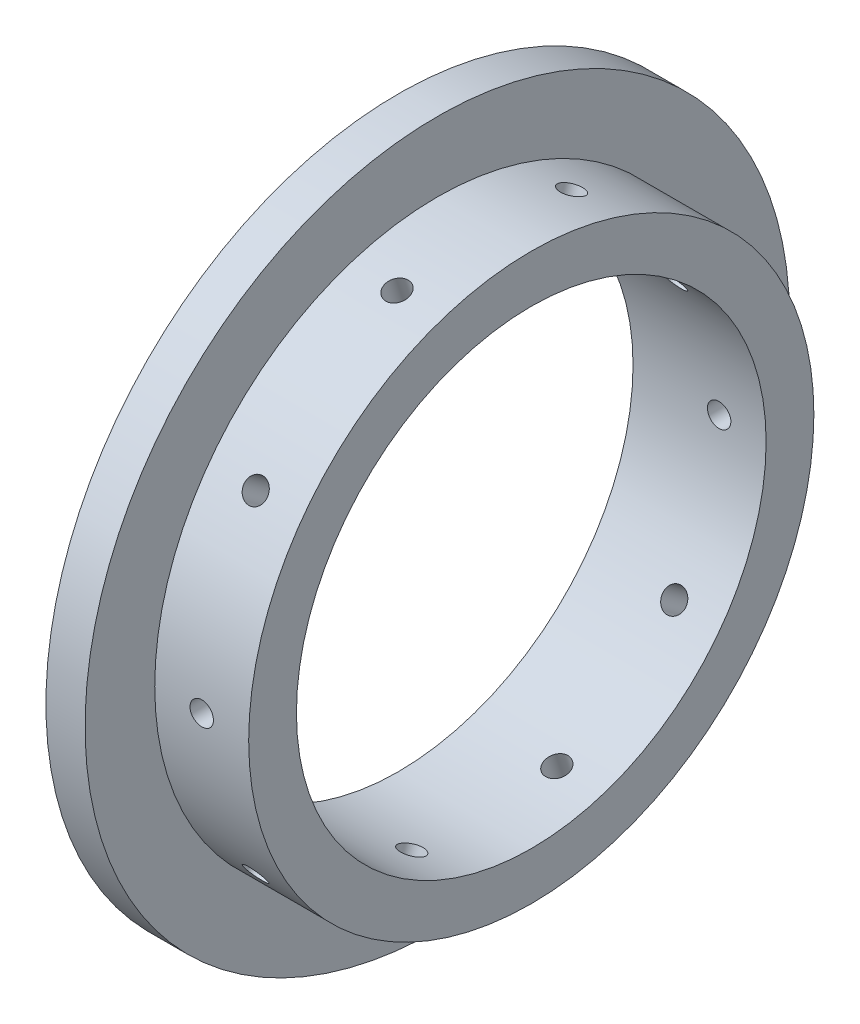
SolidWorks part; units mm, degrees
material "Alloy Steel"
ref_plane "Front Plane" through (0, 0, 0) normal (0, 0, 1) x (1, 0, 0)
ref_plane "Top Plane" through (0, 0, 0) normal (0, 1, 0) x (1, 0, 0)
ref_plane "Right Plane" through (0, 0, 0) normal (1, 0, 0) x (0, 0, -1)
sketch "Sketch1" plane through (0, 0, 0) normal (1, 0, 0) x (0, 0, -1)
  circle A0 centre (0, 0) radius 38.1
  circle A1 centre (0, 0) radius 57.15
  dimension "D1" = 76.2
  dimension "D2" = 114.3
extrude "Boss-Extrude1" add sketch "Sketch1" along normal blind 6.35
sketch "Sketch2" plane through (6.35, 0, 0) normal (1, 0, 0) x (0, 0, -1)
  circle A0 centre (0, 0) radius 45.847
  circle A1 centre (0, 0) radius 38.1
  dimension "D1" = 91.694
  dimension "D2" = 76.2
extrude "Boss-Extrude2" add sketch "Sketch2" along normal blind 15.24
sketch "Sketch3" plane through (0, 0, 0) normal (0, 1, 0) x (1, 0, 0)
  line L0 (0, 0) -> (88.5884, 0) construction
  line L1 (-13.97, 0) -> (13.97, 0) construction
  line L2 (0, 0) -> (0, 82.8947) construction
ref_plane "Plane1" through (0, 0, -45.847) normal (0, 0, -1) x (-1, 0, 0)
sketch "Sketch4" plane through (0, 0, -45.847) normal (0, 0, -1) x (-1, 0, 0)
  line L0 (0, 0) -> (-88.5884, 0) construction
  line L2 (-6.35, 45.847) -> (-6.35, -45.847) construction
  circle A0 centre (-13.97, 0) radius 1.8986
  dimension "D2" = 3.7973
  dimension "D1" = 7.62
extrude "Cut-Extrude1" cut sketch "Sketch4" against normal blind 11.43
pattern_circular "CirPattern1" count 10 over 360 about axis through (0, 0, 0) along (1, 0, 0) of "Cut-Extrude1"
